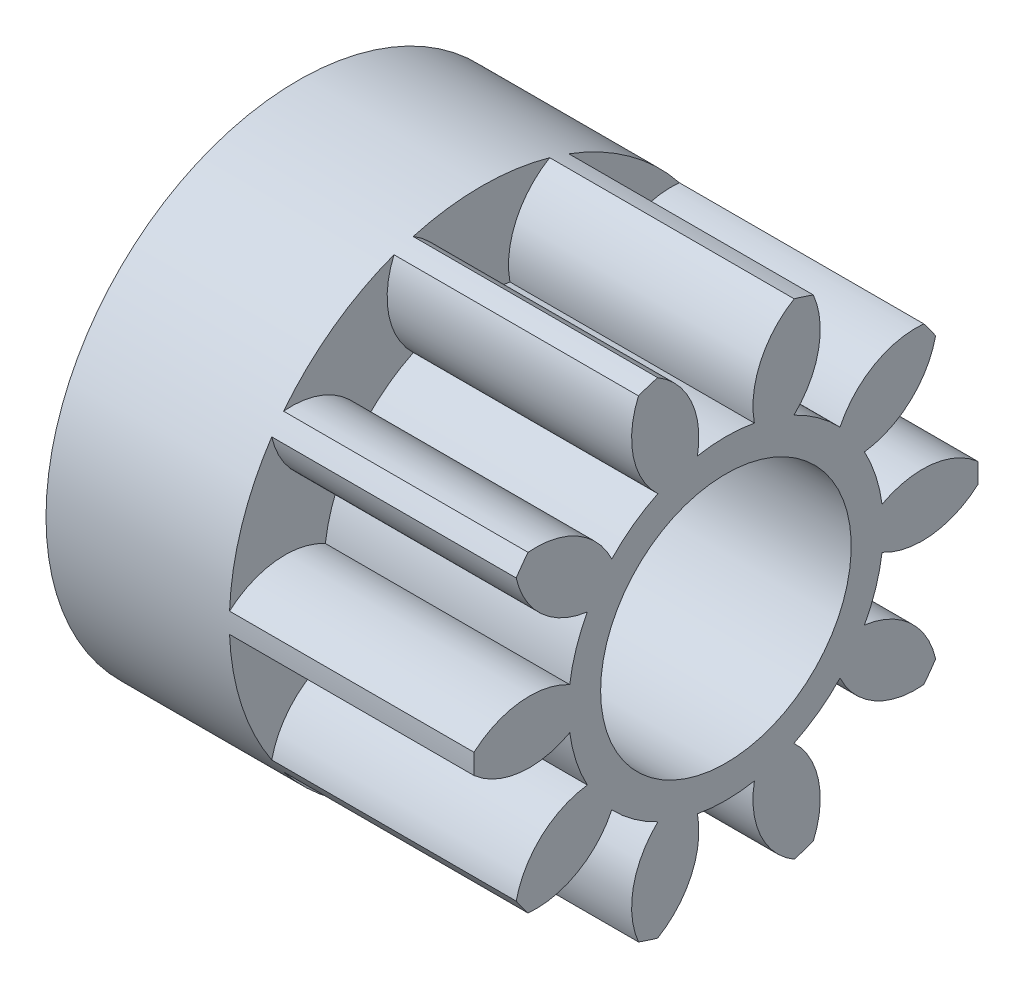
SolidWorks part; units mm, degrees
ref_plane "Plane1" through (0, 0, 0) normal (0, 0, 1) x (1, 0, 0)
ref_plane "Plane2" through (0, 0, 0) normal (0, 1, 0) x (1, 0, 0)
ref_plane "Plane3" through (0, 0, 0) normal (1, 0, 0) x (0, 0, -1)
sketch "HoldingSke" plane through (0, 0, 0) normal (0, 1, 0) x (1, 0, 0)
  line L0 (0, 0) -> (0.7162, -0.1263)
  line L1 (-15, 0) -> (100, 0) construction
  line L2 (0, 0) -> (-2.1039, 2.3779)
  line L3 (0, 0) -> (-11.863, 4.5341)
  line L4 (0, 0) -> (8.5048, 1.4996)
  line L5 (0, 0) -> (-46.8476, -17.4728)
  line L6 (0, 0) -> (-6.6317, -4.4744)
  line L7 (-2.1039, 2.3779) -> (8.6586, 51.2059)
  line L8 (-76.2, 54.61) -> (-75.5, 54.61)
  line L9 (-67.7845, 28.3722) -> (-49.3413, 33.142)
  line L10 (-76.2, 71.12) -> (104.1128, 71.12)
  line L11 (0, 0) -> (-8, 0)
  line L12 (-76.2, 101.6) -> (-76.151, 101.6)
  line L13 (24.9733, 27.94) -> (52.9518, 28.4284)
  line L14 (24.9733, 27.94) -> (24.9743, 27.94)
  line L15 (24.9733, 27.94) -> (100.4006, 29.5858)
  line L16 (-63.627, -1.375) -> (-12.827, -1.375)
  circle A0 centre (0, 0) radius 4.1
  circle A1 centre (0, 0) radius 5.1553
  circle A2 centre (0, 0) radius 37.5
  circle A3 centre (0, 0) radius 4.1
  dimension "Num_teeth" = 10
  dimension "Pitch_radius" = 180.3128
  dimension "Width" = 8
  dimension "Thickness" = 8
sketch "BasProSke" plane through (0, 0, 0) normal (0, 1, 0) x (1, 0, 0)
  line L0 (-10, 0) -> (60, 0) construction
  line L1 (0, 0) -> (0, 8.25)
  line L2 (0, 0) -> (8, 0)
  line L3 (8, 0) -> (8, 8.25)
  line L4 (8, 8.25) -> (0, 8.25)
  dimension "Thickness" = 8
  dimension "Diameter" = 16.5
revolve "Base-Revolve" add sketch "BasProSke" angle 360 about L0
sketch "TooCutSke" plane through (0, 0, 0) normal (1, 0, 0) x (0, 0, -1)
  line L1 (0, 0) -> (0, 107) construction
  line L2 (0, 0) -> (-1.1611, 6.7762) construction
  line L3 (0, 0) -> (-4.2047, 12.9408) construction
  line L4 (-1.1611, 6.7762) -> (-2.1024, 6.4704) construction
  arc A0 (0.932, 5.0703) -> (-0.932, 5.0703) centre (0, 0) ccw
  arc A1 (2.2643, 7.9596) -> (-2.2643, 7.9596) centre (0, 0) ccw
  circle A2 centre (0, 0) radius 6.875 construction
  circle A3 centre (0, 0) radius 6.656 construction
  arc A4 (-0.932, 5.0703) -> (-2.2643, 7.9596) centre (-3.6352, 5.5757) ccw
  arc A5 (2.2643, 7.9596) -> (0.932, 5.0703) centre (3.6352, 5.5757) ccw
extrude "ToothCut" cut sketch "TooCutSke" along normal through all
fillet "Breaks" [suppressed] radius 0.0275 tangent propagation no
fillet "RootFillets" [suppressed] radius 0.3448
pattern_circular "TeethCuts" count 10 every 36 about axis through (-10, 0, 0) along (1, 0, 0) of "ToothCut", "RootFillets", "Breaks"
sketch "HubNeaOneSke" plane through (0, 0, 0) normal (-1, 0, 0) x (0, 0, 1)
  circle A0 centre (0, 0) radius 5.1553
  dimension "Diameter" = 10.3105
extrude "HubNearOne" [suppressed] add sketch "HubNeaOneSke" along normal blind 42.0001
sketch "HubNeaBotSke" plane through (0, 0, 0) normal (-1, 0, 0) x (0, 0, 1)
  circle A0 centre (0, 0) radius 5.1553
  dimension "Diameter" = 10.3105
extrude "HubNearBoth" [suppressed] add sketch "HubNeaBotSke" along normal blind 21
ref_plane "FarPln" through (8, 0, 0) normal (1, 0, 0) x (0, 0, -1)
sketch "HubFarSke" plane through (8, 0, 0) normal (1, 0, 0) x (0, 0, -1)
  circle A0 centre (0, 0) radius 5.1553
  dimension "Diameter" = 10.3105
extrude "HubFar" [suppressed] add sketch "HubFarSke" along normal blind 21
sketch "BorSke" plane through (0, 0, 0) normal (1, 0, 0) x (0, 0, -1)
  circle A0 centre (0, 0) radius 4.1
  dimension "Diameter" = 8.2
extrude "Bore" cut sketch "BorSke" along normal mid plane 100.0001
sketch "KeySke" plane through (0, 0, 0) normal (1, 0, 0) x (0, 0, -1)
  line L0 (-0.8, 0) -> (-0.8, 4.8)
  line L1 (-0.8, 4.8) -> (0.8, 4.8)
  line L2 (0.8, 4.8) -> (0.8, 0)
  line L3 (0, 0) -> (0, 34) construction
  line L4 (-0.8, 0) -> (0.8, 0)
  dimension "Width" = 1.6
extrude "Keyway" [suppressed] cut sketch "KeySke" along normal mid plane 100.0001
pattern_circular "Keyway2" [suppressed] count 2 every 90 about axis through (-10, 0, 0) along (1, 0, 0) reverse direction yes
sketch "草图1" plane through (0, 0, 0) normal (-1, 0, 0) x (0, 0, 1)
  circle A0 centre (0, 0) radius 8.25
  circle A3 centre (0, 0) radius 4.1 construction
  circle A4 centre (0, 0) radius 4.1
extrude "凸台-拉伸3" add sketch "草图1" along normal blind 6
sketch "草图2" plane through (0, 0, 0) normal (0, 1, 0) x (1, 0, 0)
  circle A0 centre (-3, 0) radius 1.5
  dimension "D1" = 3
extrude "切除-拉伸1" cut sketch "草图2" against normal blind 16
equation "' \"Module@HoldingSke\" = 6.35"
equation "' \"Num_teeth@HoldingSke\" = 12"
equation "' \"Ap@HoldingSke\" =  20"
equation "' \"Ap@HoldingSke\" = 20"
equation "' \"Width@HoldingSke\" = 0.5 * 25.4"
equation "' \"Hub_dia@HoldingSke\"= 1 * 25.4"
equation "' \"Hub_dia@HoldingSke\" = 1 * 25.4"
equation "' \"Overall_len@HoldingSke\" = 1.0 * 25.4"
equation "' \"Bore@HoldingSke\" = 0.75 * 25.4"
equation "' \"T_dim@HoldingSke\" = 0.1 * 25.4"
equation "' \"Width@KeySke\" = 0.25 * 25.4"
equation "' \"Show_teeth@HoldingSke\" = 13"
equation "' \"Backlash@HoldingSke\" = 0.009 * 25.4"
equation "' \"Addendum_fac@HoldingSke\" = 1.0"
equation "' \"Dedendum_fac@HoldingSke\" = 1.25"
equation "' \"Dedendum_add@HoldingSke\" = 0.00005 * 25.4"
equation "' \"Clearance_fac@HoldingSke\" = 0.25"
equation "\"Pitch@HoldingSke\" = 1 / \"Module@HoldingSke\""
equation "\"Overcut_dia@TooCutSke\" = (\"Num_teeth@HoldingSke\" + 2 * \"Addendum_fac@HoldingSke\") / \"Pitch@HoldingSke\" + 0.002 * 25.4"
equation "\"Pitch_dia@TooCutSke\" = \"Num_teeth@HoldingSke\" / \"Pitch@HoldingSke\""
equation "\"Base_dia@TooCutSke\" = \"Num_teeth@HoldingSke\" / \"Pitch@HoldingSke\" * cos((\"Ap@HoldingSke\"  * 3.14159265 / 180))"
equation "\"Root_dia@TooCutSke\" = (\"Num_teeth@HoldingSke\" + 2) / \"Pitch@HoldingSke\" - 2 * (\"Addendum_fac@HoldingSke\" + \"Dedendum_fac@HoldingSke\") / \"Pitch@HoldingSke\" - \"Dedendum_add@HoldingSke\" * 2"
equation "\"Half_ang@TooCutSke\" = 180 / \"Num_teeth@HoldingSke\""
equation "\"Half_CT@TooCutSke\" = \"Num_teeth@HoldingSke\" / \"Pitch@HoldingSke\" * sin((3.14159265 / 2 / \"Num_teeth@HoldingSke\")) / 2 - 7 * \"Backlash@HoldingSke\" / 4"
equation "\"Flank_rad@TooCutSke\" = \"Num_teeth@HoldingSke\" / \"Pitch@HoldingSke\" / 5"
equation "\"Radius@RootFillets\" = \"Clearance_fac@HoldingSke\" / \"Pitch@HoldingSke\" + \"Dedendum_add@HoldingSke\""
equation "\"Break_rad@Breaks\" = 0.02 / \"Pitch@HoldingSke\""
equation "\"Thickness@HoldingSke\" = \"Width@HoldingSke\""
equation "\"OAL@HoldingSke\" = \"Thickness@HoldingSke\""
equation "\"MHD@HoldingSke\" = (\"Num_teeth@HoldingSke\" + 2) / \"Pitch@HoldingSke\" - 2 * (\"Addendum_fac@HoldingSke\" + \"Dedendum_fac@HoldingSke\")  / \"Pitch@HoldingSke\" - \"Dedendum_add@HoldingSke\" * 2"
equation "\"MBD@HoldingSke\" = (\"Num_teeth@HoldingSke\" + 2) / \"Pitch@HoldingSke\" - 2 * (\"Addendum_fac@HoldingSke\" + \"Dedendum_fac@HoldingSke\")  / \"Pitch@HoldingSke\" - \"Dedendum_add@HoldingSke\" * 2 - 0.002 * 25.4"
equation "\"MHD@HoldingSke\" = ((sgn( \"MHD@HoldingSke\" - \"Hub_dia@HoldingSke\" )-1)*( \"MHD@HoldingSke\" - \"Hub_dia@HoldingSke\" ))/-2+ \"Hub_dia@HoldingSke\""
equation "\"MBD@HoldingSke\" = ((sgn( \"MBD@HoldingSke\" - \"Bore@HoldingSke\" )-1)*( \"MBD@HoldingSke\" - \"Bore@HoldingSke\" ))/-2+ \"Bore@HoldingSke\""
equation "\"OAL@HoldingSke\" = ((sgn( \"OAL@HoldingSke\" - \"Overall_len@HoldingSke\" )+1)*( \"OAL@HoldingSke\" - \"Overall_len@HoldingSke\" ))/2 + \"Overall_len@HoldingSke\" + 0.000002 * 25.4"
equation "\"Num_teeth@TeethCuts\" = int( \"Show_teeth@HoldingSke\" ) + 1"
equation "\"Num_teeth@TeethCuts\" = ((sgn( \"Num_teeth@TeethCuts\" - \"Num_teeth@HoldingSke\" )-1)*( \"Num_teeth@TeethCuts\" - \"Num_teeth@HoldingSke\" ))/-2+ \"Num_teeth@HoldingSke\""
equation "\"Num_teeth@TeethCuts\" = ((sgn( \"Num_teeth@TeethCuts\" - 2.0)+1)*( \"Num_teeth@TeethCuts\" - 2.0))/2 +2.0"
equation "\"Angle@TeethCuts\" = 360.0 / \"Num_teeth@HoldingSke\""
equation "\"Diameter@BasProSke\" = (\"Num_teeth@HoldingSke\" + 2 * \"Addendum_fac@HoldingSke\") / \"Pitch@HoldingSke\""
equation "\"Thickness@BasProSke\"  = \"Thickness@HoldingSke\""
equation "' \"Fillet_rad@BasProSke\" =  \"Thickness@HoldingSke\" * 0.05"
equation "' \"Fillet_rad@BasProSke\" = \"Thickness@HoldingSke\" * 0.05"
equation "\"MHD@HoldingSke\" = ((sgn( \"MHD@HoldingSke\" - \"Root_dia@TooCutSke\" )-1)*( \"MHD@HoldingSke\" - \"Root_dia@TooCutSke\" ))/-2+ \"Root_dia@TooCutSke\""
equation "\"Diameter@HubNeaOneSke\" = \"MHD@HoldingSke\""
equation "\"Length@HubNearOne\" = \"OAL@HoldingSke\" - \"Thickness@BasProSke\""
equation "\"Diameter@HubNeaBotSke\" = \"MHD@HoldingSke\""
equation "\"Length@HubNearBoth\" = ( \"OAL@HoldingSke\" - \"Thickness@BasProSke\" ) / 2.0"
equation "\"Thickness@FarPln\" = \"Thickness@BasProSke\""
equation "\"Diameter@HubFarSke\" = \"MHD@HoldingSke\""
equation "\"Length@HubFar\" = ( \"OAL@HoldingSke\" - \"Thickness@BasProSke\" ) / 2.0"
equation "\"Diameter@BorSke\" = \"MBD@HoldingSke\""
equation "\"D1@Bore\" = \"OAL@HoldingSke\" * 2.0"
equation "\"D1@Keyway\" = \"OAL@HoldingSke\" * 2.0"
equation "\"Offset@KeySke\" = \"T_dim@HoldingSke\" + \"MBD@HoldingSke\" / 2.0"
